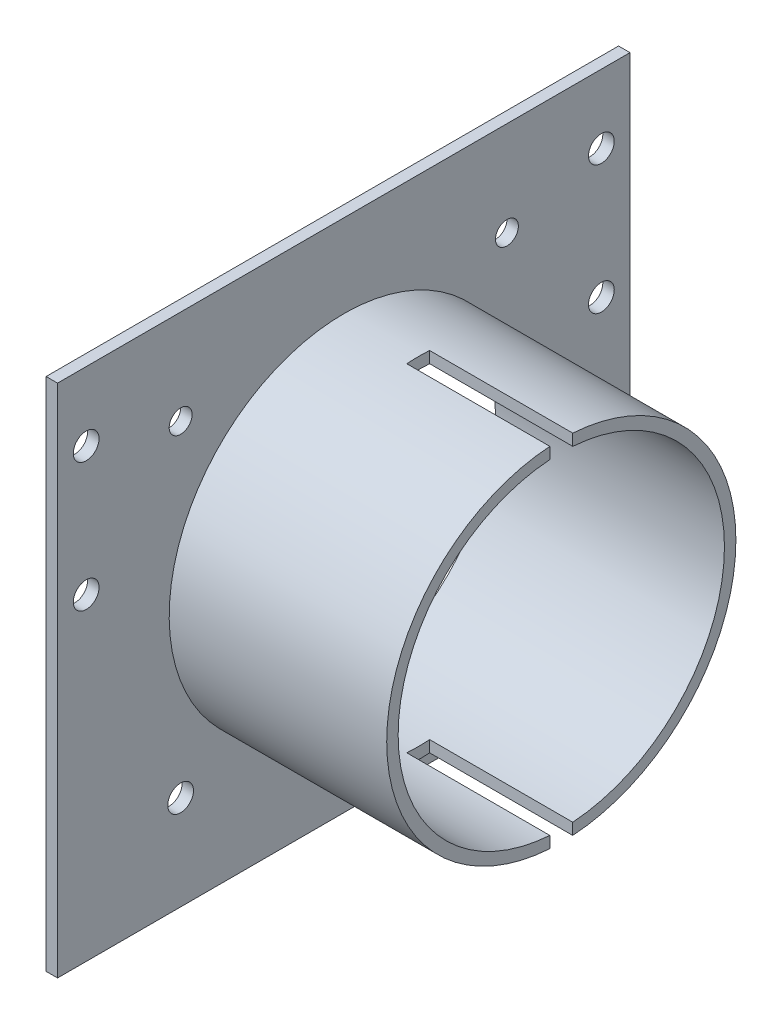
SolidWorks part; units mm, degrees
material "PVC Rígido"
ref_plane "Alzado" through (0, 0, 0) normal (0, 0, 1) x (1, 0, 0)
ref_plane "Planta" through (0, 0, 0) normal (0, 1, 0) x (1, 0, 0)
ref_plane "Vista lateral" through (0, 0, 0) normal (1, 0, 0) x (0, 0, -1)
sketch "Croquis1" plane through (0, 0, 0) normal (1, 0, 0) x (0, 0, -1)
  line L0 (0, 90) -> (0, -90) construction
  line L1 (-100, 90) -> (100, 90)
  line L2 (-100, 90) -> (-100, -90)
  line L3 (-100, -90) -> (100, -90)
  line L4 (100, 90) -> (100, -90)
  line L5 (-100, 90) -> (100, -90) construction
  line L6 (-100, -90) -> (100, 90) construction
  line L7 (57, -57) -> (-57, -57) construction
  line L8 (57, -57) -> (57, 57) construction
  line L9 (57, 57) -> (-57, 57) construction
  line L10 (-57, -57) -> (-57, 57) construction
  line L11 (57, -57) -> (-57, 57) construction
  line L12 (57, 57) -> (-57, -57) construction
  line L13 (-100, 0) -> (100, 0) construction
  circle A0 centre (0, 0) radius 57
  circle A1 centre (-57, 57) radius 4
  circle A2 centre (57, 57) radius 4
  circle A3 centre (57, -57) radius 4
  circle A4 centre (-57, -57) radius 4
  point P0 (0, 0)
  dimension "D2" = 180
  dimension "D1" = 200
extrude "Saliente-Extruir1" add sketch "Croquis1" along normal blind 4
sketch "Croquis2" plane through (4, 0, 0) normal (1, 0, 0) x (0, 0, -1)
  circle A0 centre (0, 0) radius 57
  circle A1 centre (0, 0) radius 61
  dimension "D1" = 4
extrude "Saliente-Extruir2" add sketch "Croquis2" along normal blind 76
sketch "Croquis3" plane through (80, 0, 0) normal (1, 0, 0) x (0, 0, -1)
  line L0 (-57, 0) -> (57, 0) construction
  line L1 (4, -68.5818) -> (-4, -45.4182) construction
  line L2 (4, 45.4182) -> (-4, 45.4182)
  line L3 (4, 45.4182) -> (4, 68.5818)
  line L4 (4, 68.5818) -> (-4, 68.5818)
  line L5 (-4, 45.4182) -> (-4, 68.5818)
  line L6 (4, 45.4182) -> (-4, 68.5818) construction
  line L7 (4, 68.5818) -> (-4, 45.4182) construction
  line L8 (4, -45.4182) -> (-4, -68.5818) construction
  line L9 (-4, -45.4182) -> (-4, -68.5818)
  line L10 (4, -68.5818) -> (-4, -68.5818)
  line L11 (4, -45.4182) -> (-4, -45.4182)
  line L12 (4, -45.4182) -> (4, -68.5818)
  circle A0 centre (0, 0) radius 57 construction
  point P5 (0, 57)
  point P14 (0, -57)
  dimension "D1" = 8
extrude "Cortar-Extruir1" cut sketch "Croquis3" against normal blind 50
hole_wizard "Taladro de margen para M81" positions "Croquis4" profile "Croquis5" hole size "M8" standard "Ansi Metric"
sketch "Croquis4" plane through (4, -7.4173, -252.7608) normal (1, 0, 0) x (0, 0, -1)
  point P0 (-342.7608, 73.4147)
  point P3 (-342.7608, 28.4147)
  point P6 (-162.7608, 73.4147)
  point P9 (-162.7608, 28.4147)
  point P12 (-195.7608, -49.5827)
  point P15 (-309.7608, -49.5827)
sketch "Croquis5" plane through (4, 65.9974, 90) normal (0, 1, 0) x (0, 0, -1)
  line L0 (0, 0) -> (0, 4.999)
  line L1 (0, 4.999) -> (4.5, 4.999)
  line L2 (4.5, 4.999) -> (4.5, 0)
  line L5 (4.5, 0) -> (0, 0)
  line L11 (0, -6.35) -> (0, 107.95) construction
  dimension "Diámetro de taladro hasta el siguiente" = 9
  dimension "Profundidad de taladro hasta el siguiente" = 4.999
